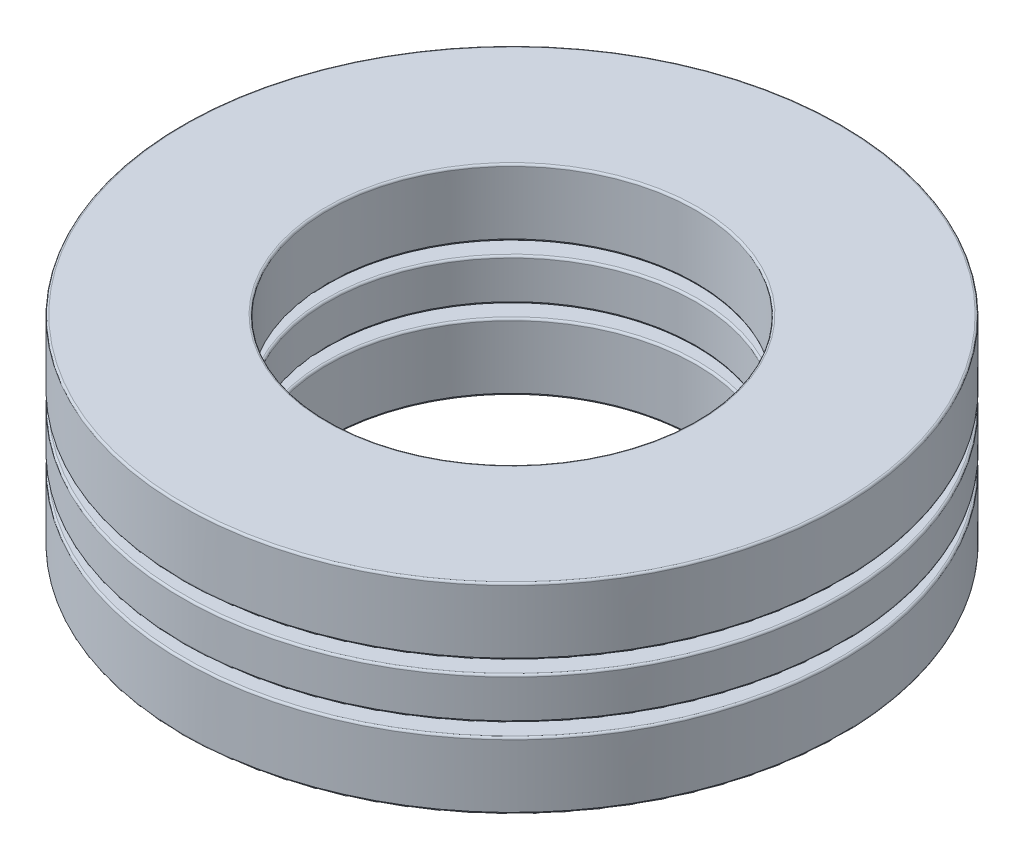
SolidWorks part; units mm, degrees
ref_plane "Front Plane" through (0, 0, 0) normal (0, 0, 1) x (1, 0, 0)
ref_plane "Top Plane" through (0, 0, 0) normal (0, 1, 0) x (1, 0, 0)
ref_plane "Right Plane" through (0, 0, 0) normal (1, 0, 0) x (0, 0, -1)
sketch "Sketch1" plane through (0, 0, 0) normal (1, 0, 0) x (0, 0, -1)
  line L0 (-14.2875, 0) -> (14.2875, 0) construction
  line L1 (0, -4.3434) -> (0, 4.3434) construction
  line L2 (-14.2875, 0.9049) -> (-7.9756, 0.9049)
  line L3 (-14.2875, 0.9049) -> (-14.2875, -0.9049)
  line L4 (-14.2875, -0.9049) -> (-7.9756, -0.9049)
  line L5 (-7.9756, 0.9049) -> (-7.9756, -0.9049)
  line L6 (-11.1315, 1.4478) -> (-11.1315, -1.4478) construction
  circle A0 centre (-11.1315, 0) radius 1.4478 construction
  point P13 (-11.1315, 0.9049)
  dimension "OD" = 28.575
  dimension "Shaft Dia" = 15.9512
  dimension "Th" = 8.6868
  dimension "D1" = 2.8956
  dimension "D2" = 1.8098
revolve "Revolve1" add sketch "Sketch1" angle 360 about L1
sketch "Sketch3" plane through (0, 0, 0) normal (1, 0, 0) x (0, 0, -1)
  line L0 (-11.1315, 1.4478) -> (-11.1315, -1.4478)
  arc A0 (-11.1315, 1.4478) -> (-11.1315, -1.4478) centre (-11.1315, 0) ccw
  circle A1 centre (-11.1315, 0) radius 1.4478 construction
revolve "Cut-Revolve1" cut sketch "Sketch3" angle 360 about L0
sketch "Sketch2" plane through (0, 0, 0) normal (1, 0, 0) x (0, 0, -1)
  line L0 (-11.1315, 1.4478) -> (-11.1315, -1.4478)
  arc A0 (-11.1315, 1.4478) -> (-11.1315, -1.4478) centre (-11.1315, 0) ccw
  circle A2 centre (-11.1315, 0) radius 1.4478 construction
revolve "Revolve2" add sketch "Sketch2" angle 360 about L0
ref_axis "Axis1" through (0, 4.3434, 0) along (0, -1, 0)
pattern_circular "CirPattern1" count 6 every 60 about axis through (0, 4.3434, 0) along (0, -1, 0) of bodies 187
pattern_circular "CirPattern2" count 6 every 60 about axis through (0, 4.3434, 0) along (0, -1, 0) of "Cut-Revolve1"
sketch "Sketch4" plane through (0, 0, 0) normal (1, 0, 0) x (0, 0, -1)
  line L0 (-14.2875, 0.9049) -> (-14.2875, -0.9049) construction
  line L1 (-14.2875, 1.4478) -> (-7.9756, 1.4478)
  line L2 (-14.2875, 1.4478) -> (-14.2875, 4.3434)
  line L3 (-14.2875, 4.3434) -> (-7.9756, 4.3434)
  line L4 (-7.9756, 1.4478) -> (-7.9756, 4.3434)
  line L5 (-14.2875, -4.3434) -> (-7.9756, -4.3434)
  line L6 (-14.2875, -4.3434) -> (-14.2875, -1.4478)
  line L7 (-14.2875, -1.4478) -> (-7.9756, -1.4478)
  line L8 (-7.9756, -4.3434) -> (-7.9756, -1.4478)
  line L9 (-11.1315, 1.4478) -> (-11.1315, -1.4478) construction
  line L10 (-7.9756, 0.9049) -> (-7.9756, -0.9049) construction
  line L11 (0, 0) -> (-14.2875, 0) construction
  line L12 (-14.2875, 0) -> (14.2875, 0) construction
  dimension "Ht" = 8.6868
revolve "Revolve3" add sketch "Sketch4" angle 360 about L1
fillet "Fillet1" radius 0.0869 4 edges at (0, 1.4478, -7.9756) (0, 4.3434, -7.9756) (0, 1.4478, -14.2875) (0, 4.3434, -14.2875)
fillet "Fillet2" radius 0.0869 4 edges at (0, -0.9049, -7.9756) (0, 0.9049, -7.9756) (0, -0.9049, -14.2875) (0, 0.9049, -14.2875)
fillet "Fillet3" radius 0.0869 4 edges at (0, -4.3434, -7.9756) (0, -1.4478, -7.9756) (0, -4.3434, -14.2875) (0, -1.4478, -14.2875)
equation "\"D1@Sketch1\" = \"Th@Sketch1\"/3"
equation "\"D2@Sketch1\" = \"D1@Sketch1\"*.625"
equation "\"Balls@CirPattern1\" = \"OD@Sketch1\"*5"
equation "\"Angle@CirPattern1\" = 360/\"Balls@CirPattern1\""
equation "\"D1@CirPattern2\" = \"Balls@CirPattern1\""
equation "\"D2@CirPattern2\" = \"Angle@CirPattern1\""
equation "\"D1@Fillet1\" = \"Th@Sketch1\"*.01"
equation "\"D1@Fillet2\" = \"D1@Fillet1\""
equation "\"D1@Fillet3\" = \"D1@Fillet1\""
